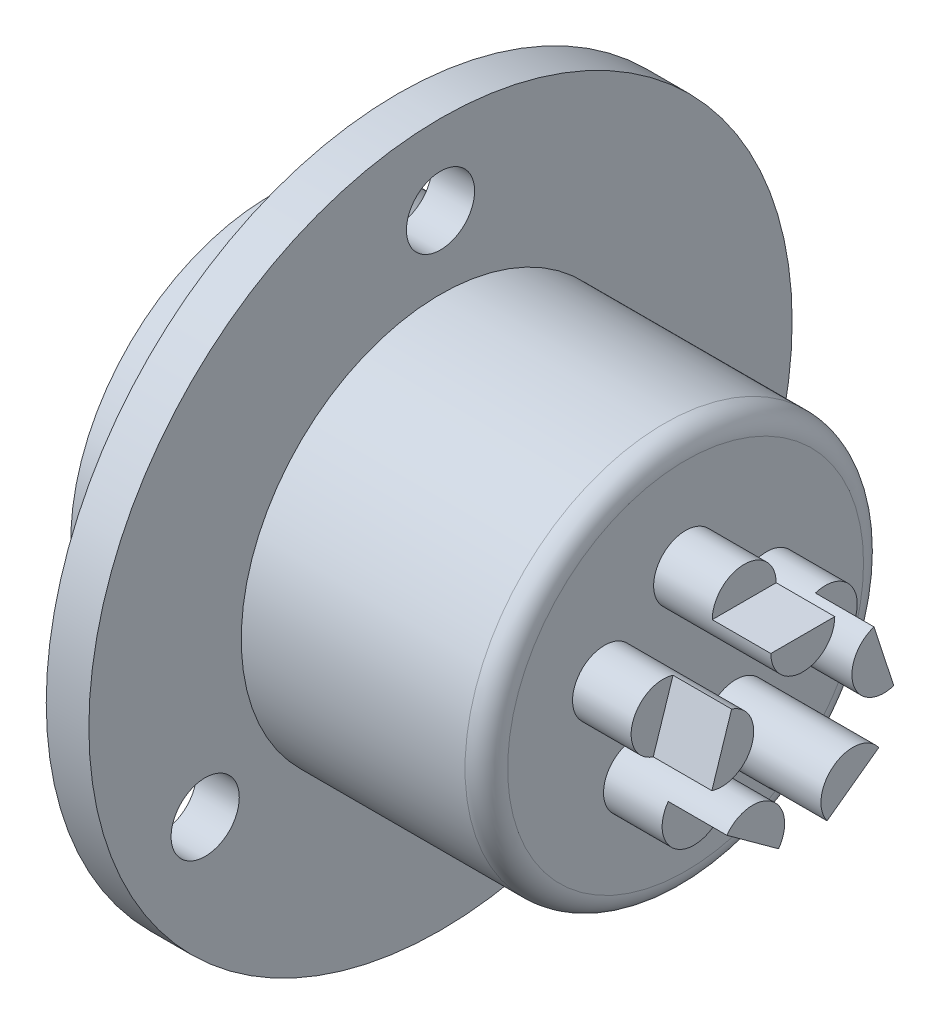
SolidWorks part; units mm, degrees
ref_plane "Ebene vorne" through (0, 0, 0) normal (0, 0, 1) x (1, 0, 0)
ref_plane "Ebene oben" through (0, 0, 0) normal (0, 1, 0) x (1, 0, 0)
ref_plane "Ebene rechts" through (0, 0, 0) normal (1, 0, 0) x (0, 0, -1)
sketch "Skizze1" plane through (0, 0, 0) normal (0, 0, 1) x (1, 0, 0)
  line L0 (0, 0) -> (6, 0)
  line L1 (6, 0) -> (6, 7.15)
  line L2 (6, 7.15) -> (8, 7.15)
  line L3 (8, 7.15) -> (8, 0)
  line L4 (8, 0) -> (19.5, 0)
  line L5 (19.5, 0) -> (19.5, -9.35)
  line L6 (19.5, -9.35) -> (0, -9.35)
  line L7 (0, -9.35) -> (0, 0)
  dimension "D1" = 9.35
  dimension "D2" = 16.5
  dimension "D3" = 9.35
  dimension "D4" = 6
  dimension "D5" = 2
  dimension "D6" = 11.5
revolve "Rotation1" add sketch "Skizze1" angle 360 about L6
sketch "Skizze2" plane through (19.5, 0, 0) normal (-1, 0, 0) x (0, 0, 1)
  circle A0 centre (0, -9.35) radius 4 construction
  circle A1 centre (0, -5.35) radius 1.5
  dimension "D1" = 8
  dimension "D2" = 3
extrude "Aufsatz-Linear austragen1" add sketch "Skizze2" against normal blind 5.5
ref_plane "Ebene1" through (0, -3.85, 0) normal (0, 1, 0) x (1, 0, 0)
sketch "Skizze3" plane through (0, -3.85, 0) normal (0, 1, 0) x (1, 0, 0)
  line L0 (25, 1.5) -> (19.5, 1.5) construction
  line L1 (25, -1.5) -> (22.25, -1.5)
  line L2 (25, -1.5) -> (25, 1.5)
  line L3 (25, 1.5) -> (22.25, 1.5)
  line L4 (22.25, -1.5) -> (22.25, 1.5)
extrude "Schnitt-Linear austragen1" cut sketch "Skizze3" against normal blind 1.5
pattern_circular "Kreismuster1" count 5 over 360 about axis through (19.5, -9.35, 0) along (1, 0, 0) of "Aufsatz-Linear austragen1", "Schnitt-Linear austragen1"
sketch "Skizze4" plane through (6, 0, 0) normal (1, 0, 0) x (0, 0, -1)
  line L0 (0, -9.35) -> (11.0418, -15.725) construction
  line L1 (0, 3.4) -> (0, -9.35) construction
  line L2 (0, -9.35) -> (-11.0418, -15.725) construction
  circle A0 centre (0, -9.35) radius 12.75 construction
  circle A1 centre (0, 3.4) radius 1.6
  circle A2 centre (11.0418, -15.725) radius 1.6
  circle A3 centre (-11.0418, -15.725) radius 1.6
  dimension "D1" = 3.2
  dimension "D2" = 120
  dimension "D4" = 25.5
  dimension "D3" = 120
extrude "Schnitt-Linear austragen5" cut sketch "Skizze4" along normal through all
sketch "Skizze5" plane through (0, 0, 0) normal (-1, 0, 0) x (0, 0, 1)
  circle A0 centre (0, -9.35) radius 8
  dimension "D1" = 16
extrude "Schnitt-Linear austragen6" cut sketch "Skizze5" against normal blind 13
fillet "Verrundung1" radius 1 1 edges at (19.5, -9.35, -9.35)
ref_axis "Achse1" through (8, 3.4, 0) along (-1, 0, 0)
ref_plane "Ebene2" through (0, 3.4, 0) normal (0, 1, 0) x (1, 0, 0)
